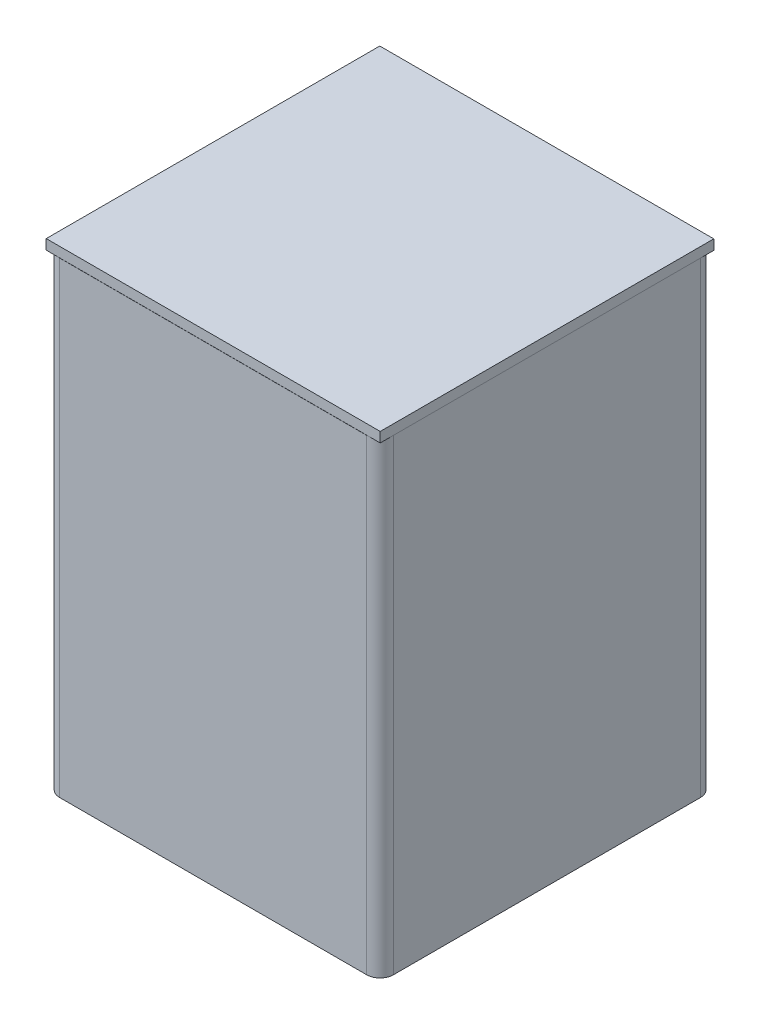
SolidWorks part; units mm, degrees
ref_plane "Front Plane" through (0, 0, 0) normal (0, 0, 1) x (1, 0, 0)
ref_plane "Top Plane" through (0, 0, 0) normal (0, 1, 0) x (1, 0, 0)
ref_plane "Right Plane" through (0, 0, 0) normal (1, 0, 0) x (0, 0, -1)
sketch "Sketch10" plane through (0, 0, 0) normal (0, 1, 0) x (1, 0, 0)
  line L1 (-67.9796, 19.3986) -> (59.0204, 19.3986)
  line L2 (-67.9796, 19.3986) -> (-67.9796, -107.6014)
  line L3 (-67.9796, -107.6014) -> (59.0204, -107.6014)
  line L4 (59.0204, 19.3986) -> (59.0204, -107.6014)
  dimension "D1" = 127
  dimension "D2" = 127
extrude "Boss-Extrude1" add sketch "Sketch10" along normal blind 177.8
sketch "Sketch11" plane through (0, 177.8, 0) normal (0, 1, 0) x (1, 0, 0)
  line L0 (59.0204, 19.3986) -> (-67.9796, 19.3986) construction
  line L1 (-64.1696, 15.5886) -> (55.2104, 15.5886)
  line L2 (-64.1696, 15.5886) -> (-64.1696, -103.7914)
  line L3 (-64.1696, -103.7914) -> (55.2104, -103.7914)
  line L4 (55.2104, 15.5886) -> (55.2104, -103.7914)
  line L5 (59.0204, -107.6014) -> (59.0204, 19.3986) construction
  line L6 (-67.9796, -107.6014) -> (59.0204, -107.6014) construction
  line L7 (-67.9796, 19.3986) -> (-67.9796, -107.6014) construction
  dimension "D1" = 3.81
  dimension "D2" = 3.81
  dimension "D3" = 3.81
  dimension "D4" = 3.81
extrude "Cut-Extrude6" cut sketch "Sketch11" against normal blind 173.99
fillet "Fillet1" radius 5.08 4 edges at (-67.9796, 88.9, -19.3986) (59.0204, 88.9, -19.3986) (59.0204, 88.9, 107.6014) (-67.9796, 88.9, 107.6014)
sketch "Sketch13" plane through (0, 177.8, 0) normal (0, 1, 0) x (1, 0, 0)
  line L1 (-62.8996, 14.3186) -> (53.9404, 14.3186)
  line L2 (-62.8996, 14.3186) -> (-62.8996, -102.5214)
  line L3 (-62.8996, -102.5214) -> (53.9404, -102.5214)
  line L4 (53.9404, 14.3186) -> (53.9404, -102.5214)
  line L5 (-64.1696, -103.7914) -> (55.2104, -103.7914) construction
  line L8 (55.2104, -103.7914) -> (55.2104, 15.5886) construction
  dimension "D1" = 1.27
  dimension "D2" = 1.27
extrude "Boss-Extrude2" add sketch "Sketch13" against normal blind 12.7 separate body contours L2 L1 L4 L3
sketch "Sketch15" plane through (0, 177.8, 0) normal (0, 1, 0) x (1, 0, 0)
  line L1 (59.0204, 19.3986) -> (-68.0927, 19.3986)
  line L2 (59.0204, 19.3986) -> (59.0204, -107.5419)
  line L3 (59.0204, -107.5419) -> (-68.0927, -107.5419)
  line L4 (-68.0927, 19.3986) -> (-68.0927, -107.5419)
extrude "Boss-Extrude4" add sketch "Sketch15" along normal blind 3.81 separate body contours L2 L1 L4 L3
combine bodies "Combine1" operation type add bodies to combine 113 111
